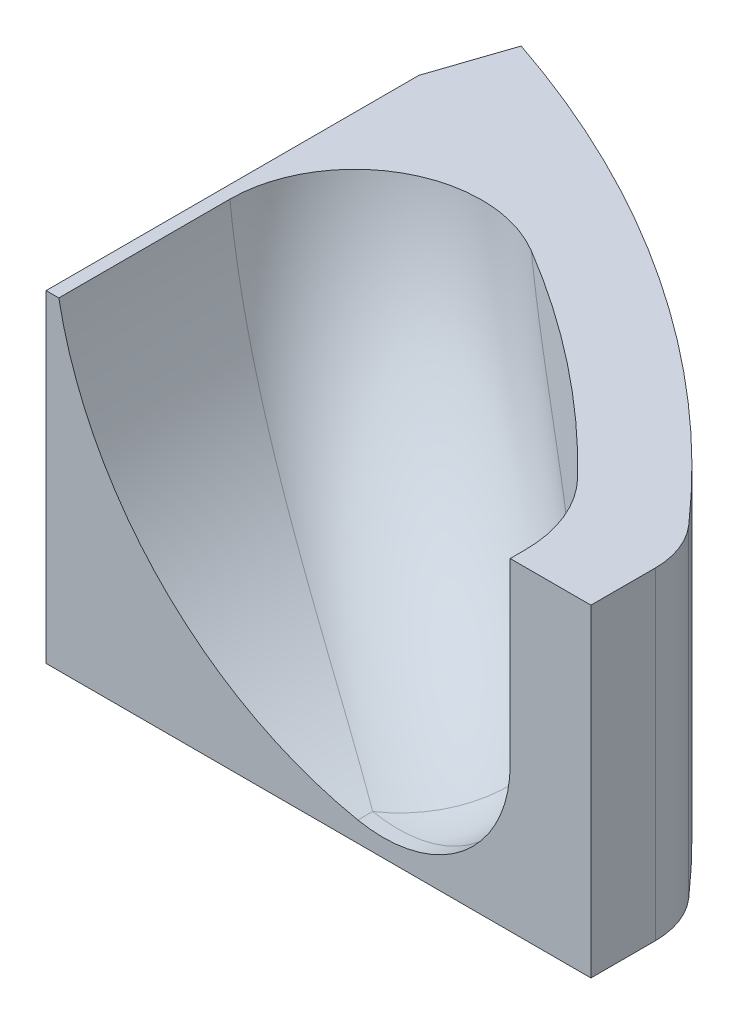
SolidWorks part; units mm, degrees
ref_plane "Front Plane" through (0, 0, 0) normal (0, 0, 1) x (1, 0, 0)
ref_plane "Top Plane" through (0, 0, 0) normal (0, 1, 0) x (1, 0, 0)
ref_plane "Right Plane" through (0, 0, 0) normal (1, 0, 0) x (0, 0, -1)
sketch "Sketch2" plane through (0, 0, 0) normal (0, 1, 0) x (1, 0, 0)
  line L0 (0, 0) -> (84.665, 0) construction
  line L1 (0, 0) -> (63.4984, 56.0011) construction
  line L2 (0, 0) -> (0, 84.665) construction
  line L5 (26.9907, 80.2475) -> (29.015, 86.2662)
  line L7 (63.4984, 56.0011) -> (63.4984, 50.9211)
  line L8 (63.4984, 50.9211) -> (69.8484, 50.9211)
  line L9 (69.8484, 56.0011) -> (69.8484, 50.9211)
  line L10 (26.9907, 80.2475) -> (0, 0) construction
  arc A0 (63.4984, 56.0011) -> (26.9907, 80.2475) centre (0, 0) ccw
  arc A1 (68.2609, 60.2012) -> (29.015, 86.2662) centre (0, 0) ccw
  arc A2 (68.2609, 60.2012) -> (69.8484, 56.0011) centre (63.4984, 56.0011) cw
  arc A3 (63.4984, 56.0011) -> (0, 84.665) centre (0, 0) ccw construction
  arc A4 (68.2609, 60.2012) -> (0, 91.015) centre (0, 0) ccw construction
  point P13 (0, 0)
  point P14 (37.536, 82.9143)
  dimension "D1" = 169.33
  dimension "D6" = 30
  dimension "D2" = 41.41
  dimension "D3" = 6.35
  dimension "D4" = 5.08
  dimension "D5" = 6.35
extrude "Boss-Extrude1" add sketch "Sketch2" along normal blind 25.4
fillet "Fillet1" radius 10 1 edges at (63.4984, 12.7, -56.0011)
sketch "Sketch3" plane through (0, 0, 0) normal (0, -1, 0) x (1, 0, 0)
  line L0 (63.4984, -52.0844) -> (63.4984, -50.9211) construction
  line L1 (63.4984, -50.9211) -> (26.9907, -50.9211)
  line L4 (26.9907, -50.9211) -> (26.9907, -80.2475)
  line L5 (63.4984, -52.0844) -> (63.4984, -50.9211)
  arc A0 (60.6635, -59.0602) -> (63.4984, -52.0844) centre (53.4984, -52.0844) ccw construction
  arc A1 (26.9907, -80.2475) -> (60.6635, -59.0602) centre (0, 0) ccw construction
  arc A2 (60.6635, -59.0602) -> (63.4984, -52.0844) centre (53.4984, -52.0844) ccw
  arc A3 (26.9907, -80.2475) -> (60.6635, -59.0602) centre (0, 0) ccw
  point P0 (0, 0)
extrude "Boss-Extrude2" add sketch "Sketch3" against normal blind 1
sketch "Sketch4" plane through (0, 1, 0) normal (0, 1, 0) x (1, 0, 0)
  line L1 (26.9907, 50.9211) -> (27.9907, 50.9211)
  line L2 (26.9907, 50.9211) -> (26.9907, 80.2475)
  line L3 (26.9907, 80.2475) -> (27.9907, 80.2475)
  line L4 (27.9907, 50.9211) -> (27.9907, 80.2475)
  point P4 (26.9907, 80.2475)
  dimension "D1" = 1
extrude "Boss-Extrude3" add sketch "Sketch4" along normal up to surface (24.4 mm away) up to face at (56.9583, 25.4, -62.5893)
fillet "Fillet4" radius 30 1 edges at (27.9907, 1, -65.4126)
fillet "Fillet5" radius 10 3 edges at (63.4984, 1, -51.5027) (59.084, 1, -60.6403) (36.8863, 9.1692, -76.2074)
